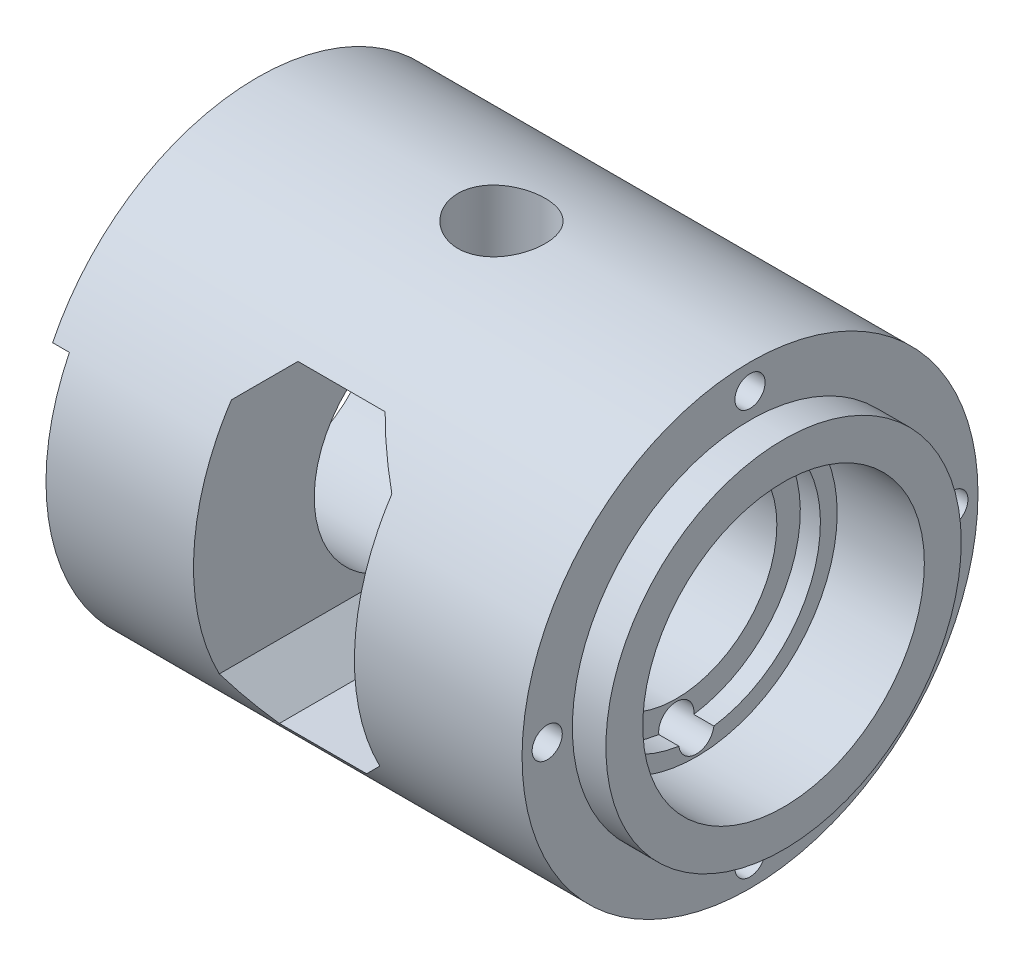
SolidWorks part; units mm, degrees
ref_plane "Front Plane" through (0, 0, 0) normal (0, 0, 1) x (1, 0, 0)
ref_plane "Top Plane" through (0, 0, 0) normal (0, 1, 0) x (1, 0, 0)
ref_plane "Right Plane" through (0, 0, 0) normal (1, 0, 0) x (0, 0, -1)
sketch "Sketch17" plane through (0, 0, 0) normal (0, 0, 1) x (1, 0, 0)
  line L0 (0, 0) -> (156.5215, 0) construction
sketch "Sketch1" plane through (0, 0, 0) normal (1, 0, 0) x (0, 0, -1)
  circle A0 centre (0, 0) radius 68
extrude "Boss-Extrude1" add sketch "Sketch1" along normal blind 157 contours A0
sketch "Sketch2" plane through (0, 0, 0) normal (-1, 0, 0) x (0, 0, 1)
  circle A0 centre (0, 0) radius 26
extrude "Cut-Extrude1" cut sketch "Sketch2" against normal up to next
sketch "Sketch3" plane through (0, 0, 0) normal (-1, 0, 0) x (0, 0, 1)
  line L1 (-68, 30) -> (68, 30)
  line L2 (-68, 30) -> (-68, -68)
  line L3 (-68, -68) -> (68, -68)
  line L4 (68, 30) -> (68, -68)
  circle A2 centre (0, 0) radius 68 construction
  circle A3 centre (0, 0) radius 26 construction
  dimension "D1" = 30
  dimension "D2" = 68
  dimension "D3" = 42
  dimension "D4" = 68
  dimension "D5" = 68
extrude "Cut-Extrude2" cut sketch "Sketch3" against normal blind 5 contours L2 L3 L4 L1
sketch "Sketch4" plane through (5, 0, 0) normal (-1, 0, 0) x (0, 0, 1)
  line L3 (-13.5, 29) -> (13.5, 29)
  arc A2 (13.5, 29) -> (-13.5, 29) centre (0, 0) cw
  dimension "D1" = 27
  dimension "D2" = 29
extrude "Cut-Extrude3" cut sketch "Sketch4" against normal blind 44
sketch "Sketch7" plane through (157, 0, 0) normal (1, 0, 0) x (0, 0, -1)
  circle A0 centre (0, 0) radius 42
extrude "Cut-Extrude4" cut sketch "Sketch7" against normal blind 26
sketch "Sketch8" plane through (131, 0, 0) normal (1, 0, 0) x (0, 0, -1)
  circle A0 centre (0, 0) radius 37
extrude "Cut-Extrude5" cut sketch "Sketch8" against normal blind 6 contours A0
sketch "Sketch9" plane through (125, 0, 0) normal (1, 0, 0) x (0, 0, -1)
  circle A0 centre (0, 0) radius 30
extrude "Cut-Extrude6" cut sketch "Sketch9" against normal blind 28 contours A0
ref_plane "Plane2" through (0, 0, 68) normal (0, 0, 1) x (1, 0, 0)
sketch "Sketch12" plane through (0, 0, 68) normal (0, 0, 1) x (1, 0, 0)
  line L0 (49, 37.576) -> (49, -31.4216)
  line L1 (49, -31.4216) -> (59.8739, -42.2955)
  line L2 (59.8739, -42.2955) -> (85.8739, -42.2955)
  line L3 (85.8739, -42.2955) -> (97, -31.1695)
  line L4 (97, -31.1695) -> (97, 37.3239)
  line L5 (97, 37.3239) -> (85.8739, 48.4499)
  line L6 (85.8739, 48.4499) -> (59.8739, 48.4499)
  line L7 (59.8739, 48.4499) -> (49, 37.576)
  line L8 (157, -68) -> (157, 68) construction
  line L9 (5, 30) -> (5, -68) construction
  dimension "D1" = 60
  dimension "D2" = 44
  dimension "D3" = 26
  dimension "D4" = 26
  dimension "D5" = 135
  dimension "D6" = 135
  dimension "D7" = 135
  dimension "D8" = 135
extrude "Cut-Extrude8" cut sketch "Sketch12" against normal blind 71 contours L0 L1 L2 L3 L4 L5 L6 L7
sketch "Sketch16" plane through (0, 0, 0) normal (-1, 0, 0) x (0, 0, 1)
  line L0 (35.9404, 57.726) -> (61.0246, 30) construction
  line L1 (35.9404, 57.726) -> (0, 68) construction
  arc A0 (61.0246, 30) -> (-61.0246, 30) centre (0, 0) ccw construction
  dimension "D1" = 37.38
  dimension "D2" = 37.3892
ref_plane "Plane5" through (0, 68, 0) normal (0, 1, 0) x (1, 0, 0)
sketch "Sketch23" plane through (0, 68, 0) normal (0, 1, 0) x (1, 0, 0)
  point P9 (72.8739, 0)
  dimension "D1" = 13
hole_wizard "Tap Drill for M1.2x0.25 Tap1" positions "Sketch23" profile "Sketch26" hole size "M1.2x0.25" standard "ISO"
sketch "Sketch26" plane through (72.8739, 68, 0) normal (1, 0, 0) x (0, 0, 1)
  line L0 (0, 0) -> (0, 68)
  line L1 (0, 68) -> (13, 68)
  line L2 (13, 68) -> (13, 0)
  line L5 (13, 0) -> (0, 0)
  line L10 (0, 68) -> (-13, 68) construction
  line L11 (0, -6.35) -> (0, 107.95) construction
  dimension "Hole Dia." = 26
  dimension "Hole Depth" = 68
  dimension "Drill Angle" = 180
sketch "Sketch27" plane through (157, 0, 0) normal (1, 0, 0) x (0, 0, -1)
  circle A0 centre (0, 0) radius 68
  circle A1 centre (0, 0) radius 53
  dimension "D1" = 136
  dimension "D2" = 106
extrude "Cut-Extrude9" cut sketch "Sketch27" against normal blind 10
sketch "Sketch29" plane through (147, 0, 0) normal (1, 0, 0) x (0, 0, -1)
  line L0 (0, 68) -> (0, 53) construction
  line L1 (53, 0) -> (68, 0) construction
  line L2 (0, -53) -> (0, -68) construction
  line L3 (-53, 0) -> (-68, 0) construction
  line L4 (-68, 74.8) -> (-68, -74.8) construction
  circle A0 centre (0, 0) radius 53 construction
  circle A1 centre (0, 0) radius 53 construction
  circle A2 centre (0, 0) radius 68 construction
  point P21 (0, 60.5)
  point P23 (60.5, 0)
  point P25 (0, -60.5)
  point P27 (-60.5, 0)
hole_wizard "M8 Clearance Hole1" positions "Sketch29" profile "Sketch30" hole size "M8" standard "ISO"
sketch "Sketch30" plane through (147, 0, 60.5) normal (0, 1, 0) x (0, 0, -1)
  line L0 (0, 0) -> (0, 37.7039)
  line L1 (0, 37.7039) -> (4.5, 35)
  line L2 (4.5, 35) -> (4.5, 0)
  line L5 (4.5, 0) -> (0, 0)
  line L10 (0, 37.7039) -> (-4.5, 35) construction
  line L11 (0, -6.35) -> (0, 107.95) construction
  dimension "Hole Dia." = 9
  dimension "Hole Depth" = 35
  dimension "Drill Angle" = 118
ref_plane "Plane4" [suppressed] through (0, 0, 0) normal (0, 0.5285, -0.8489) x (-1, 0, 0)
sketch "Sketch19" [suppressed] plane through (0, 0, 0) normal (0, 0.5285, -0.8489) x (-1, 0, 0)
  line L3 (-27.3689, 310) -> (-67.3689, 310)
  line L7 (-97, 30.0991) -> (-97, 61.7272) construction
  line L8 (-49, 30.3131) -> (-49, 61.8533) construction
  line L9 (0, 0) -> (-156.5215, 0) construction
  line L10 (-67.3689, 310) -> (-95.5, 66.5)
  line L11 (-95.5, 66.5) -> (-50.5, 66.5)
  line L12 (-50.5, 66.5) -> (-27.3689, 310)
  line L13 (0, 68) -> (-147, 68) construction
  dimension "D2" = 48
  dimension "D1" = 310
  dimension "D3" = 45
  dimension "D4" = 1.5
  dimension "D5" = 1.5
  dimension "D6" = 40
sketch "Sketch21" [suppressed] plane through (0, 0, 0) normal (0, 0.5285, -0.8489) x (-1, 0, 0)
  line L0 (-67.3689, 310) -> (-69.3689, 310)
  line L1 (-69.3689, 310) -> (-69.3689, 340)
  line L2 (-69.3689, 340) -> (-92.3689, 340)
  line L3 (-92.3689, 340) -> (-92.3689, 350)
  line L4 (-92.3689, 350) -> (-59.3689, 350)
  line L5 (-2.3689, 350) -> (-2.3689, 340)
  line L6 (-2.3689, 340) -> (-25.3689, 340)
  line L7 (-25.3689, 340) -> (-25.3689, 310)
  line L8 (-25.3689, 310) -> (-27.3689, 310)
  line L11 (-59.3689, 350) -> (-59.3689, 320)
  line L12 (-59.3689, 320) -> (-35.3689, 320)
  line L13 (-35.3689, 320) -> (-35.3689, 350)
  line L14 (-35.3689, 350) -> (-2.3689, 350)
  line L15 (-27.3689, 310) -> (-67.3689, 310) construction
  line L17 (-67.3689, 310) -> (-27.3689, 310)
  dimension "D2" = 10
  dimension "D3" = 10
  dimension "D7" = 10
  dimension "D8" = 90
  dimension "D11" = 40
  dimension "D12" = 40
  dimension "D10" = 2
  dimension "D6" = 10
  dimension "D9" = 10
  dimension "D4" = 23
  dimension "D13" = 24
revolve "Revolve1" [suppressed] add sketch "Sketch21" angle 360 about L0
extrude "Boss-Extrude4" [suppressed] add sketch "Sketch19" along normal mid plane 10
pattern_circular "CirPattern4" [suppressed] count 3 over 360 about axis through (0, 0, 0) along (1, 0, 0) of bodies 117
sketch "Esquisse4" plane through (131, 0, 0) normal (1, 0, 0) x (0, 0, -1)
  line L0 (0, 0) -> (0, -36) construction
  point P11 (0, -36)
  dimension "D1" = 36
  dimension "D2" = 0
hole_wizard "M10 Clearance Hole1" positions "Esquisse4" profile "Esquisse6" hole size "M10" standard "ANSI Metric"
sketch "Esquisse6" plane through (131, -36, 0) normal (0, 1, 0) x (0, 0, -1)
  line L0 (0, 0) -> (0, 15)
  line L1 (0, 15) -> (5.25, 15)
  line L2 (5.25, 15) -> (5.25, 0)
  line L5 (5.25, 0) -> (0, 0)
  line L10 (0, 15) -> (-5.25, 15) construction
  line L11 (0, -6.35) -> (0, 107.95) construction
  dimension "Hole Dia." = 10.5
  dimension "Hole Depth" = 15
  dimension "Drill Angle" = 180
equation "\"D1@Sketch3\"=26+8/2"
equation "\"D2@Sketch3\"=26+\"D3@Sketch3\""
equation "\"D4@Sketch3\"=\"D2@Sketch3\""
equation "\"D5@Sketch3\"=\"D2@Sketch3\""
equation "\"D5@Sketch19\"=(\"D2@Sketch19\"-\"D3@Sketch19\")/2"
equation "\"D12@Sketch21\"=\"D11@Sketch21\""
equation "\"D2@Sketch27\"=\"D1@Sketch27\"-15*2"
equation "\"D4@Sketch21\"=(\"D8@Sketch21\"-\"D6@Sketch21\"-\"D13@Sketch21\"-\"D9@Sketch21\")/2"
